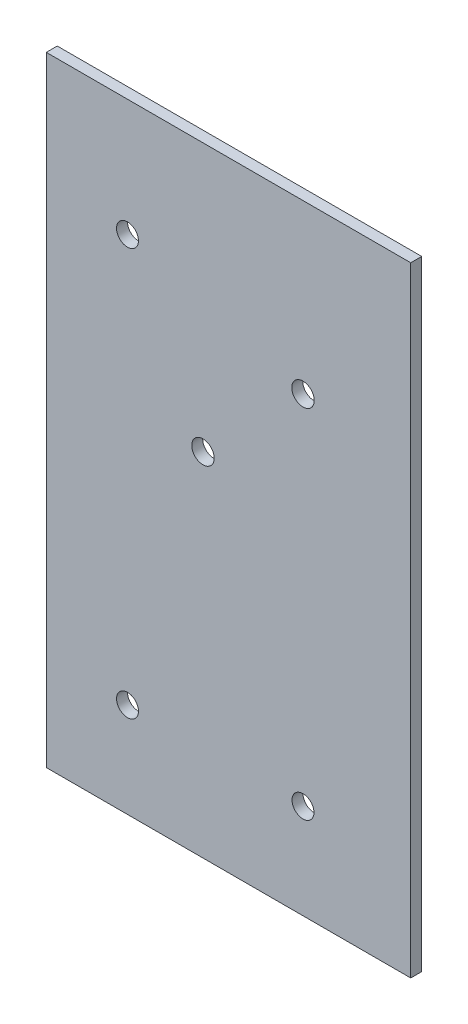
SolidWorks part; units mm, degrees
ref_plane "Front Plane" through (0, 0, 0) normal (0, 0, 1) x (1, 0, 0)
ref_plane "Top Plane" through (0, 0, 0) normal (0, 1, 0) x (1, 0, 0)
ref_plane "Right Plane" through (0, 0, 0) normal (1, 0, 0) x (0, 0, -1)
sketch "Sketch1" plane through (0, 0, 0) normal (0, 0, 1) x (1, 0, 0)
  line L1 (1.8891, 210.8161) -> (107.3869, 210.8161)
  line L2 (1.8891, 210.8161) -> (1.8891, 31.5173)
  line L3 (1.8891, 31.5173) -> (107.3869, 31.5173)
  line L4 (107.3869, 210.8161) -> (107.3869, 31.5173)
  line L5 (63.5, 146.05) -> (63.5, 120.65) construction
  line L8 (63.5, 146.05) -> (88.9, 146.05) construction
  circle A0 centre (25.4, 58.9643) radius 3.175
  circle A1 centre (76.2, 58.9643) radius 3.175
  circle A2 centre (25.4, 176.8929) radius 3.175
  circle A3 centre (47.244, 133.35) radius 3.2512
  circle A4 centre (76.2, 162.306) radius 3.2512
  dimension "D1" = 6.35
  dimension "D6" = 6.5024
  dimension "D4" = 16.256
  dimension "D7" = 33.9233
  dimension "D8" = 23.5109
  dimension "D9" = 27.447
  dimension "D10" = 31.1869
  dimension "D2" = 12.7
  dimension "D3" = 16.256
  dimension "D5" = 12.7
extrude "Boss-Extrude1" add sketch "Sketch1" along normal blind 3.175
equation "\"80/20 to Center Hole\"= .64in"
equation "\"80/20 from Edge\"= 0.5in"
equation "\"D4@Sketch1\"=\"80/20 to Center Hole\""
equation "\"D3@Sketch1\"=\"80/20 to Center Hole\""
